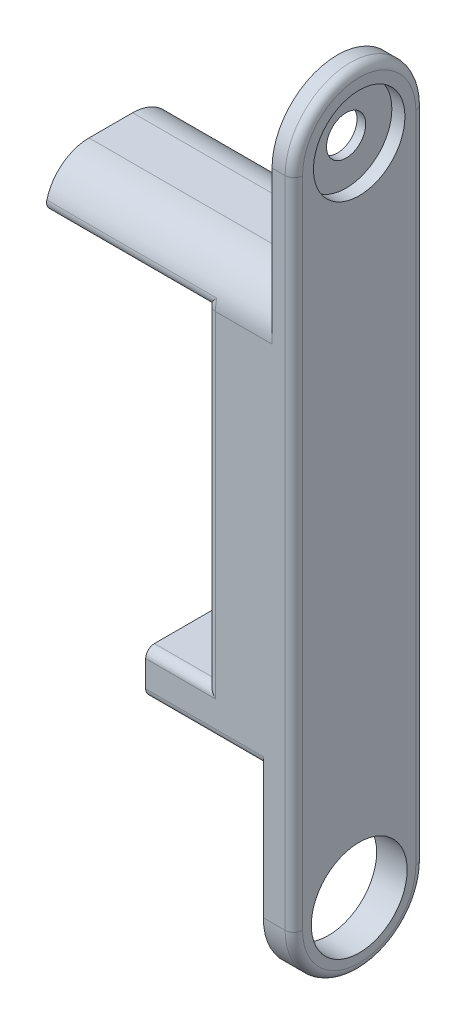
SolidWorks part; units mm, degrees
material "ABS"
ref_plane "Front" through (0, 0, 0) normal (0, 0, 1) x (1, 0, 0)
ref_plane "Top" through (0, 0, 0) normal (0, 1, 0) x (1, 0, 0)
ref_plane "Right" through (0, 0, 0) normal (1, 0, 0) x (0, 0, -1)
sketch "Sketch2" plane through (0, 0, 0) normal (0, 1, 0) x (1, 0, 0)
  line L1 (-10, -15) -> (10, -15)
  line L2 (-10, -15) -> (-10, 15)
  line L3 (-10, 15) -> (10, 15)
  line L4 (10, -15) -> (10, 15)
  point P4 (0, -15)
  point P6 (-10, 0)
  dimension "D1" = 20
  dimension "D2" = 30
extrude "Boss-Extrude1" add sketch "Sketch2" along normal blind 125
sketch "Sketch3" plane through (10, 0, 0) normal (1, 0, 0) x (0, 0, -1)
  line L0 (-15, 0) -> (15, 0) construction
  line L1 (-15, 125) -> (-15, 0) construction
  circle A0 centre (0, 0) radius 15
extrude "Boss-Extrude2" add sketch "Sketch3" against normal blind 7
sketch "Sketch4" plane through (-10, 0, 0) normal (-1, 0, 0) x (0, 0, 1)
  circle A0 centre (0, 0) radius 15
  arc A1 (-15, 0) -> (15, 0) centre (0, 0) ccw construction
extrude "Cut-Extrude1" cut sketch "Sketch4" against normal up to surface (13 mm away) up to face at (3, -7.5, 0)
sketch "Sketch8" plane through (10, 0, 0) normal (1, 0, 0) x (0, 0, -1)
  line L0 (-15, 115) -> (15, 115)
  line L1 (15, 115) -> (15, 150)
  line L2 (-15, 150) -> (-15, 115)
  line L3 (-15, 125) -> (15, 125) construction
  line L4 (-15, 125) -> (-15, 0) construction
  arc A0 (15, 150) -> (-15, 150) centre (0, 150) ccw
  point P5 (0, 115)
  point P8 (0, 125)
  dimension "D1" = 10
  dimension "D2" = 25
extrude "Boss-Extrude3" add sketch "Sketch8" against normal blind 5
sketch "Sketch11" plane through (10, 0, 0) normal (1, 0, 0) x (0, 0, -1)
  circle A0 centre (0, 150) radius 10.5
  dimension "D1" = 21
extrude "Cut-Extrude4" cut sketch "Sketch11" against normal blind 3
sketch "Sketch12" plane through (7, 0, 0) normal (1, 0, 0) x (0, 0, -1)
  circle A0 centre (0, 150) radius 4.5
  dimension "D1" = 9
extrude "Cut-Extrude5" cut sketch "Sketch12" against normal through all
sketch "Sketch13" plane through (-10, 0, 0) normal (-1, 0, 0) x (0, 0, 1)
  line L0 (-15, 125) -> (-15, 0) construction
  line L1 (15, 125) -> (-15, 125)
  line L2 (15, 125) -> (15, 115)
  line L3 (15, 115) -> (-15, 115)
  line L4 (-15, 125) -> (-15, 115)
  dimension "D1" = 10
extrude "Boss-Extrude4" add sketch "Sketch13" along normal blind 37
sketch "Sketch14" plane through (10, 0, 0) normal (1, 0, 0) x (0, 0, -1)
  circle A0 centre (0, 0) radius 11
  dimension "D1" = 22
extrude "Cut-Extrude6" cut sketch "Sketch14" against normal through all
fillet "Fillet1" radius 10 2 edges at (-21, 125, -15) (-21, 125, 15)
sketch "Sketch16" plane through (3, 0, 0) normal (-1, 0, 0) x (0, 0, 1)
  line L0 (-15, 115) -> (-15, 0) construction
  line L1 (15, 0) -> (-15, 0)
  line L2 (15, 0) -> (15, 30)
  line L3 (15, 30) -> (-15, 30)
  line L4 (-15, 0) -> (-15, 30)
  line L5 (15, 115) -> (15, 0) construction
  dimension "D1" = 30
extrude "Cut-Extrude8" cut sketch "Sketch16" along normal up to surface (13 mm away) up to face at (-10, 61.25, 0)
sketch "Sketch18" plane through (-10, 0, 0) normal (-1, 0, 0) x (0, 0, 1)
  line L0 (-15, 115) -> (-15, 30) construction
  line L1 (15, 30) -> (-15, 30)
  line L2 (15, 30) -> (15, 40)
  line L3 (15, 40) -> (-15, 40)
  line L4 (-15, 30) -> (-15, 40)
  dimension "D1" = 10
extrude "Boss-Extrude5" add sketch "Sketch18" along normal blind 14
hole_wizard "#2 Clearance Hole1" positions "Sketch19" profile "Sketch20" hole size "#2" standard "ANSI Inch"
sketch "Sketch19" plane through (-24, 0, 0) normal (-1, 0, 0) x (0, 0, 1)
  line L0 (-7.5, 35) -> (7.5, 35) construction
  line L1 (0, 35) -> (0, 30) construction
  line L2 (-15, 30) -> (15, 30) construction
  point P0 (-7.5, 35)
  point P2 (7.5, 35)
  dimension "D1" = 5
  dimension "D2" = 15
sketch "Sketch20" plane through (-24, 35, -7.5) normal (0, 1, 0) x (0, 0, 1)
  line L0 (0, 0) -> (0, 7.0826)
  line L1 (0, 7.0826) -> (1.2192, 6.35)
  line L2 (1.2192, 6.35) -> (1.2192, 0)
  line L5 (1.2192, 0) -> (0, 0)
  line L10 (0, 7.0826) -> (-1.2192, 6.35) construction
  line L11 (0, -6.35) -> (0, 107.95) construction
  dimension "Hole Dia." = 2.4384
  dimension "Hole Depth" = 6.35
  dimension "Drill Angle" = 118
sketch "Sketch21" plane through (-24, 0, 0) normal (-1, 0, 0) x (0, 0, 1)
  line L1 (7.5, 32.171) -> (9.95, 33.5855)
  line L2 (9.95, 33.5855) -> (9.95, 36.4145)
  line L3 (9.95, 36.4145) -> (7.5, 37.829)
  line L4 (7.5, 37.829) -> (5.05, 36.4145)
  line L5 (5.05, 36.4145) -> (5.05, 33.5855)
  line L6 (5.05, 33.5855) -> (7.5, 32.171)
  line L7 (-7.5, 32.171) -> (-5.05, 33.5855)
  line L8 (-5.05, 33.5855) -> (-5.05, 36.4145)
  line L9 (-5.05, 36.4145) -> (-7.5, 37.829)
  line L10 (-7.5, 37.829) -> (-9.95, 36.4145)
  line L11 (-9.95, 36.4145) -> (-9.95, 33.5855)
  line L12 (-9.95, 33.5855) -> (-7.5, 32.171)
  circle A0 centre (7.5, 35) radius 2.45 construction
  circle A1 centre (-7.5, 35) radius 2.45 construction
  dimension "D1" = 4.9
extrude "Cut-Extrude9" cut sketch "Sketch21" against normal blind 1.65 from offset 1.5 offset against normal yes
hole_wizard "#2 Clearance Hole2" positions "Sketch22" profile "Sketch23" hole size "#2" standard "ANSI Inch"
sketch "Sketch22" plane through (-47, 0, 0) normal (-1, 0, 0) x (0, 0, 1)
  line L1 (7.5, 120) -> (-7.5, 120) construction
  line L2 (0, 115) -> (0, 120) construction
  line L3 (-15, 115) -> (15, 115) construction
  point P0 (-7.5, 120)
  point P2 (7.5, 120)
  dimension "D1" = 5
  dimension "D2" = 15
sketch "Sketch23" plane through (-47, 120, -7.5) normal (0, 1, 0) x (0, 0, 1)
  line L0 (0, 0) -> (0, 7.0826)
  line L1 (0, 7.0826) -> (1.2192, 6.35)
  line L2 (1.2192, 6.35) -> (1.2192, 0)
  line L5 (1.2192, 0) -> (0, 0)
  line L10 (0, 7.0826) -> (-1.2192, 6.35) construction
  line L11 (0, -6.35) -> (0, 107.95) construction
  dimension "Hole Dia." = 2.4384
  dimension "Hole Depth" = 6.35
  dimension "Drill Angle" = 118
sketch "Sketch24" plane through (-47, 0, 0) normal (-1, 0, 0) x (0, 0, 1)
  line L1 (-7.5, 122.829) -> (-9.95, 121.4145)
  line L2 (-9.95, 121.4145) -> (-9.95, 118.5855)
  line L3 (-9.95, 118.5855) -> (-7.5, 117.171)
  line L4 (-7.5, 117.171) -> (-5.05, 118.5855)
  line L5 (-5.05, 118.5855) -> (-5.05, 121.4145)
  line L6 (-5.05, 121.4145) -> (-7.5, 122.829)
  line L7 (7.5, 122.829) -> (5.05, 121.4145)
  line L8 (5.05, 121.4145) -> (5.05, 118.5855)
  line L9 (5.05, 118.5855) -> (7.5, 117.171)
  line L10 (7.5, 117.171) -> (9.95, 118.5855)
  line L11 (9.95, 118.5855) -> (9.95, 121.4145)
  line L12 (9.95, 121.4145) -> (7.5, 122.829)
  circle A0 centre (-7.5, 120) radius 2.45 construction
  circle A1 centre (7.5, 120) radius 2.45 construction
  dimension "D1" = 4.9
extrude "Cut-Extrude10" cut sketch "Sketch24" against normal blind 1.6 from offset 2 offset against normal yes
fillet "Fillet2" radius 2 12 edges at (-10, 77.5, -15) (-10, 77.5, 15) (-28.5, 115, -15) (-28.5, 115, 15) (-17, 40, -15) (-17, 40, 15) (-10.5, 30, -15) (-10.5, 30, 15) (10, 165, 0) (10, 75, -15) (10, -15, 0) (10, 75, 15)
